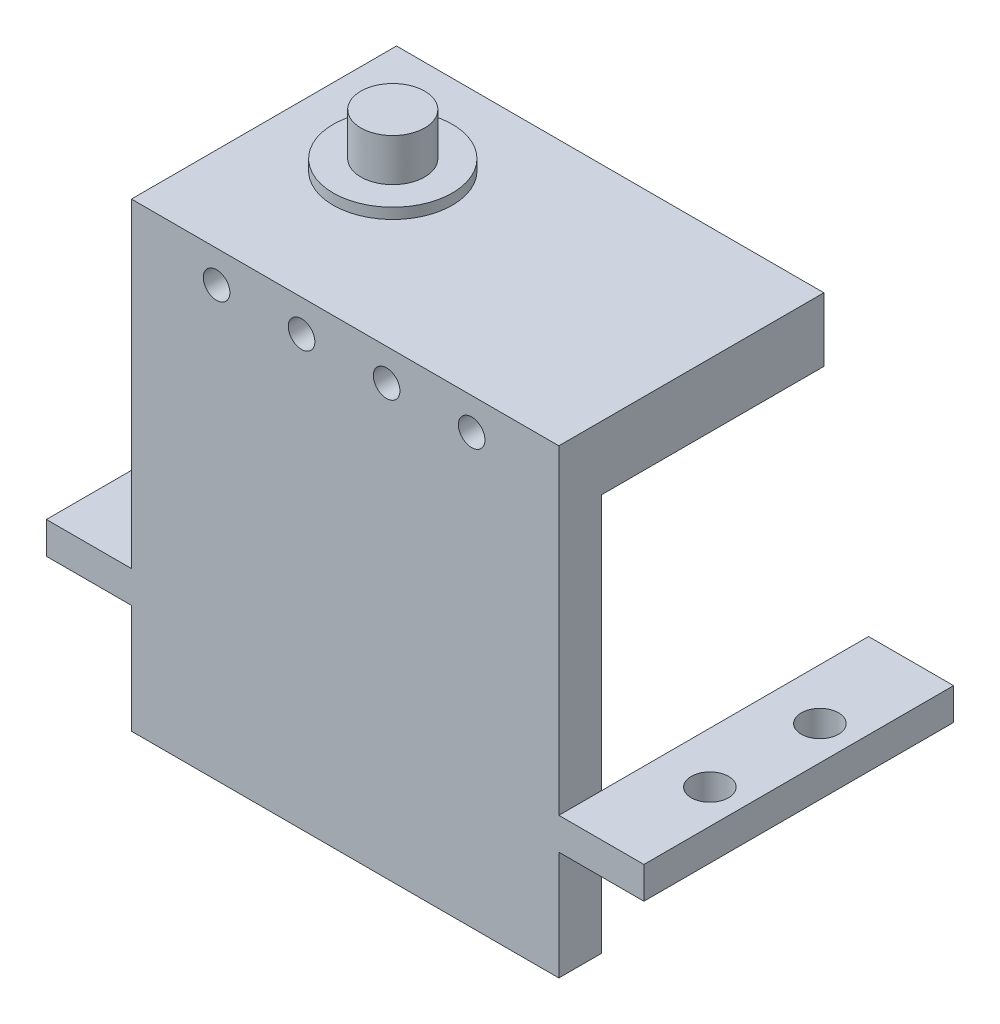
SolidWorks part; units mm, degrees
ref_plane "Front Plane" through (0, 0, 0) normal (0, 0, 1) x (1, 0, 0)
ref_plane "Top Plane" through (0, 0, 0) normal (0, 1, 0) x (1, 0, 0)
ref_plane "Right Plane" through (0, 0, 0) normal (1, 0, 0) x (0, 0, -1)
sketch "Sketch5" plane through (0, 0, 0) normal (0, 0, 1) x (1, 0, 0)
  line L0 (-138.6442, -51.4091) -> (-138.6442, -41.1591)
  line L1 (-138.6442, -41.1591) -> (-146.6442, -41.1591)
  line L2 (-146.6442, -41.1591) -> (-146.6442, -38.1591)
  line L3 (-146.6442, -38.1591) -> (-138.6442, -38.1591)
  line L4 (-138.6442, -38.1591) -> (-138.6442, -14.0591)
  line L5 (-98.4442, -38.1591) -> (-98.4442, -14.0591)
  line L6 (-98.4442, -14.0591) -> (-138.6442, -14.0591)
  line L7 (-98.4442, -38.1591) -> (-90.4442, -38.1591)
  line L8 (-90.4442, -38.1591) -> (-90.4442, -41.1591)
  line L10 (-90.4442, -41.1591) -> (-98.4442, -41.1591)
  line L11 (-98.4442, -41.1591) -> (-98.4442, -51.4091)
  line L12 (-98.4442, -51.4091) -> (-138.6442, -51.4091)
  dimension "D1" = 8
  dimension "D2" = 8
  dimension "D3" = 10.25
  dimension "D5" = 10.25
extrude "Boss-Extrude2" add sketch "Sketch5" along normal blind 4 contours L12 L11 L10 L8 L7 L2 L0 region at (-118.5442, -32.9486, 0)
sketch "Sketch6" plane through (0, 0, 0) normal (0, 0, -1) x (-1, 0, 0)
  line L1 (138.6442, -41.1591) -> (146.6442, -41.1591)
  line L2 (138.6442, -41.1591) -> (138.6442, -38.1591)
  line L3 (138.6442, -38.1591) -> (146.6442, -38.1591)
  line L4 (146.6442, -41.1591) -> (146.6442, -38.1591)
  line M4 (146.6442, -41.1591) -> (146.6442, -38.1591)
  line M22 (138.6442, -41.1591) -> (146.6442, -41.1591)
  line M23 (146.6442, -38.1591) -> (138.6442, -38.1591)
extrude "Boss-Extrude3" add sketch "Sketch6" along normal blind 25.13 contours L4 M22 M4 M23 region at (-142.6442, -39.6591, 0)
sketch "Sketch7" plane through (0, 0, 0) normal (0, 0, -1) x (-1, 0, 0)
  line L1 (90.4442, -41.1591) -> (98.4442, -41.1591)
  line L2 (90.4442, -41.1591) -> (90.4442, -38.1591)
  line L3 (90.4442, -38.1591) -> (98.4442, -38.1591)
  line L4 (98.4442, -41.1591) -> (98.4442, -38.1591)
extrude "Boss-Extrude4" add sketch "Sketch7" along normal blind 25.13
sketch "Sketch32" plane through (0, 0, 0) normal (0, 0, -1) x (-1, 0, 0)
  line L0 (138.6442, -14.0591) -> (98.4442, -14.0591)
  line L1 (98.4442, -14.0591) -> (98.4442, -8.0591)
  line L2 (98.4442, -8.0591) -> (138.6442, -8.0591)
  line L3 (138.6442, -8.0591) -> (138.6442, -14.0591)
extrude "Boss-Extrude6" add sketch "Sketch32" along normal blind 20.93
sketch "Sketch33" plane through (0.0533, -14.0591, 0) normal (0, 1, 0) x (1, 0, 0)
  circle A0 centre (-128.6162, 10.1451) radius 3.5
extrude "Boss-Extrude9" add sketch "Sketch33" along normal blind 5.05
sketch "Sketch63" plane through (0.0384, -8.0591, 0) normal (0, 1, 0) x (1, 0, 0)
  circle A0 centre (-128.6826, 10.58) radius 5.6
extrude "Boss-Extrude16" add sketch "Sketch63" along normal blind 1 separate body contours A0 | A0 region at (-128.6442, -8.0591, -10.58)
sketch "Sketch70" plane through (0, -38.1591, 0) normal (0, 1, 0) x (1, 0, 0)
  line L6 (-98.4442, 10.125) -> (-90.4442, 10.125) construction
  line L7 (-90.4442, 10.125) -> (-90.4442, 10.725) construction
  line L8 (-90.4442, 10.725) -> (-90.4442, 9.525) construction
  circle A0 centre (-93.6442, 15.755) radius 1.75
  circle A1 centre (-93.6442, 5.405) radius 1.75
extrude "Cut-Extrude23" cut sketch "Sketch70" against normal blind 5 contours A1 | A0 region at (-93.6442, -38.1591, -15.755) region at (-93.6442, -38.1591, -5.405)
sketch "Sketch71" plane through (0, -41.1591, 0) normal (0, -1, 0) x (-1, 0, 0)
  line L0 (138.6442, 10.125) -> (138.6442, 14.545) construction
  line L2 (93.6442, 15.755) -> (138.6442, 15.755) construction
  line L3 (138.6442, 10.125) -> (145.6442, 10.125) construction
  line L4 (138.6442, 15.755) -> (143.4442, 15.755) construction
  line L5 (143.4442, 15.755) -> (143.4442, 5.405) construction
  circle A0 centre (143.4442, 15.755) radius 1.75
  circle A1 centre (143.4442, 5.405) radius 1.75
extrude "Cut-Extrude24" cut sketch "Sketch71" against normal blind 6 contours A0 | A1 region at (-143.4442, -41.1591, -15.755) region at (-143.4442, -41.1591, -5.405)
sketch "Sketch86" plane through (0, 0, -20.93) normal (0, 0, -1) x (-1, 0, 0)
  circle A0 centre (130.6442, -11.0591) radius 1.25
  circle A1 centre (122.6442, -11.0591) radius 1.25
  circle A2 centre (114.6442, -11.0591) radius 1.25
  circle A3 centre (106.6442, -11.0591) radius 1.25
extrude "Cut-Extrude26" cut sketch "Sketch86" against normal blind 25 and the other way blind 10 contours A2 | A3 | A1
sketch "Sketch88" plane through (0, -14.0591, 0) normal (0, 1, 0) x (1, 0, 0)
  line L1 (-138.6442, 0) -> (-98.4442, 0)
  line L2 (-138.6442, 0) -> (-138.6442, -4)
  line L3 (-138.6442, -4) -> (-98.4442, -4)
  line L4 (-98.4442, 0) -> (-98.4442, -4)
extrude "Boss-Extrude26" add sketch "Sketch88" along normal blind 6
sketch "Sketch89" plane through (0, 0, 4) normal (0, 0, 1) x (1, 0, 0)
  circle A0 centre (-130.6363, -11.0591) radius 1.25
  circle A1 centre (-122.6442, -11.0591) radius 1.25
  circle A2 centre (-114.6442, -11.0591) radius 1.25
  circle A3 centre (-106.6442, -11.0591) radius 1.25
extrude "Cut-Extrude28" cut sketch "Sketch89" against normal blind 30 and the other way blind 4 contours A1 | A2 | A0 | A3 region at (-122.6442, -11.0591, 4) region at (-114.6442, -11.0591, 4)
sketch "Sketch90" plane through (0, -7.0591, 0) normal (0, 1, 0) x (1, 0, 0)
  circle A0 centre (-128.6442, 10.58) radius 3
extrude "Boss-Extrude27" add sketch "Sketch90" along normal blind 4 and the other way blind 2
